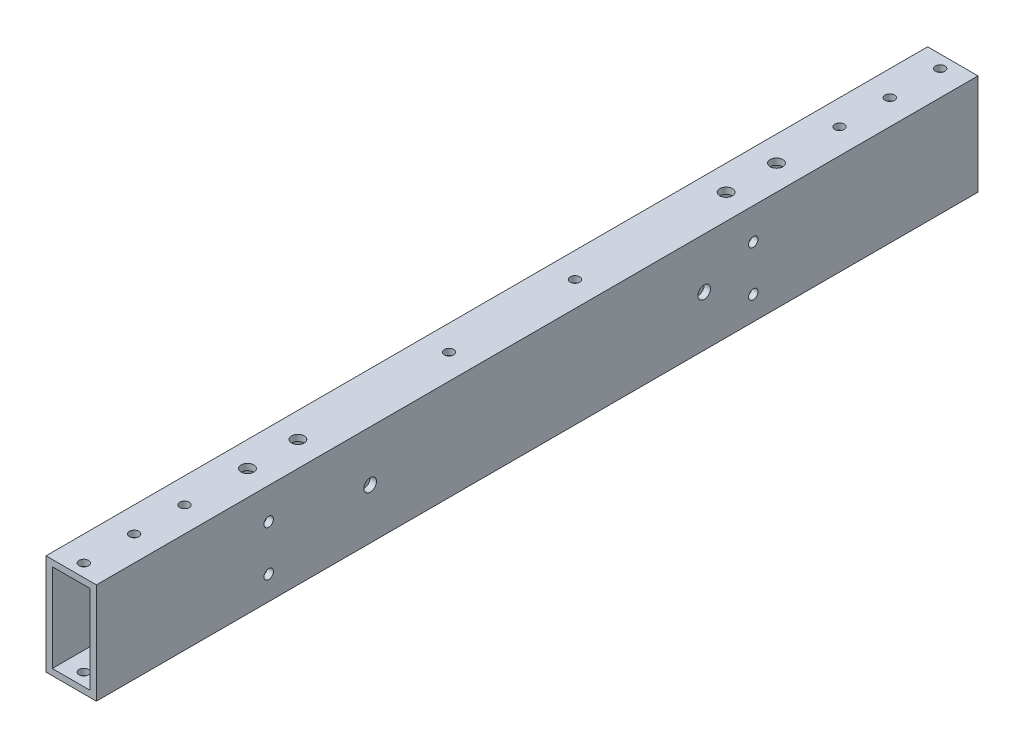
SolidWorks part; units mm, degrees
material "6063-T1"
ref_plane "Front Plane" through (0, 0, 0) normal (0, 0, 1) x (1, 0, 0)
ref_plane "Top Plane" through (0, 0, 0) normal (0, 1, 0) x (1, 0, 0)
ref_plane "Right Plane" through (0, 0, 0) normal (1, 0, 0) x (0, 0, -1)
sketch "Sketch1" plane through (0, 0, 0) normal (0, 0, 1) x (1, 0, 0)
  line L1 (-12.7, 25.4) -> (12.7, 25.4)
  line L2 (-12.7, 25.4) -> (-12.7, -25.4)
  line L3 (-12.7, -25.4) -> (12.7, -25.4)
  line L4 (12.7, 25.4) -> (12.7, -25.4)
  line L5 (-12.7, 25.4) -> (12.7, -25.4) construction
  line L6 (-12.7, -25.4) -> (12.7, 25.4) construction
  point P0 (0, 0)
  dimension "D1" = 25.4
  dimension "D2" = 50.8
extrude "Boss-Extrude1" add sketch "Sketch1" along normal blind 444.5
shell "Shell1" thickness 3.175 removed face at (0, 0, 0) removed face at (0, 0, 444.5)
sketch "Sketch2" plane through (0, 25.4, 0) normal (0, 1, 0) x (1, 0, 0)
  line L0 (12.7, 0) -> (-12.7, 0) construction
  line L1 (12.7, -222.25) -> (-14.2289, -222.25) construction
  line L2 (12.7, -444.5) -> (12.7, 0) construction
  circle A0 centre (0, -6.35) radius 2.3812
  circle A3 centre (0, -31.75) radius 2.3812
  circle A4 centre (0, -57.15) radius 2.3812
  circle A5 centre (0, -387.35) radius 2.3812
  circle A6 centre (0, -412.75) radius 2.3812
  circle A7 centre (0, -438.15) radius 2.3813
  dimension "D1" = 4.7625
  dimension "D2" = 6.35
  dimension "D3" = 3
extrude "Cut-Extrude1" cut sketch "Sketch2" against normal through all
sketch "Sketch3" plane through (-12.7, 0, 0) normal (-1, 0, 0) x (0, 0, 1)
  line L0 (222.25, 25.4) -> (222.25, -25.4) construction
  line L1 (444.5, 25.4) -> (0, 25.4) construction
  line L2 (444.5, -25.4) -> (0, -25.4) construction
  line L3 (0, 25.4) -> (0, -25.4) construction
  circle A0 centre (138.049, 0) radius 3.175
  circle A1 centre (306.451, 0) radius 3.175
  dimension "D1" = 6.35
  dimension "D2" = 138.049
  dimension "D3" = 25.4
extrude "Cut-Extrude2" cut sketch "Sketch3" against normal through all
sketch "Sketch4" plane through (0, 25.4, 0) normal (0, 1, 0) x (1, 0, 0)
  line L0 (12.7, -222.25) -> (-12.7, -222.25) construction
  line L1 (12.7, -444.5) -> (12.7, 0) construction
  line L2 (-12.7, -444.5) -> (-12.7, 0) construction
  line L3 (12.7, 0) -> (-12.7, 0) construction
  circle A0 centre (0, -190.5) radius 2.3812
  circle A1 centre (0, -254) radius 2.3813
  dimension "D1" = 4.7625
  dimension "D2" = 190.5
  dimension "D3" = 12.7
extrude "Cut-Extrude3" cut sketch "Sketch4" against normal through all
sketch "Sketch5" plane through (-12.7, 0, 0) normal (-1, 0, 0) x (0, 0, 1)
  line L1 (444.5, 25.4) -> (0, 25.4) construction
  line L2 (444.5, 25.4) -> (444.5, -25.4) construction
  line L3 (0, -25.4) -> (0, 25.4) construction
  circle A0 centre (357.632, 9.525) radius 2.3813
  circle A1 centre (357.632, -13.335) radius 2.3813
  circle A2 centre (113.284, 9.525) radius 2.3813
  circle A3 centre (113.284, -13.335) radius 2.3813
  dimension "D3" = 4.7625
  dimension "D4" = 4.7625
  dimension "D9" = 4.7625
  dimension "D10" = 4.7625
  dimension "D1" = 86.868
  dimension "D2" = 86.868
  dimension "D5" = 15.875
  dimension "D6" = 22.86
  dimension "D7" = 113.284
  dimension "D8" = 113.284
  dimension "D11" = 22.86
extrude "Cut-Extrude4" cut sketch "Sketch5" against normal through all
sketch "Sketch6" plane through (0, 25.4, 0) normal (0, 1, 0) x (1, 0, 0)
  line L0 (0, -444.5) -> (0, -342.9) construction
  line L1 (12.7, -444.5) -> (-12.7, -444.5) construction
  line L2 (0, -355.6) -> (0, -330.2) construction
  circle A0 centre (0, -330.2) radius 3.175
  circle A1 centre (0, -355.6) radius 3.175
  point P8 (0, -342.9)
  dimension "D3" = 6.35
  dimension "D4" = 6.35
  dimension "D1" = 101.6
  dimension "D2" = 12.7
extrude "Cut-Extrude5" cut sketch "Sketch6" against normal up to surface (3.175 mm away) up to face at (0, 22.225, 188.1188)
sketch "Sketch7" plane through (0, 25.4, 0) normal (0, 1, 0) x (1, 0, 0)
  line L0 (0, 0) -> (0, -101.6) construction
  line L1 (0, -114.3) -> (0, -88.9) construction
  circle A0 centre (0, -88.9) radius 3.175
  circle A1 centre (0, -114.3) radius 3.175
  point P6 (0, -101.6)
  dimension "D3" = 6.35
  dimension "D4" = 6.35
  dimension "D1" = 101.6
  dimension "D2" = 12.7
extrude "Cut-Extrude6" cut sketch "Sketch7" against normal up to surface (47.625 mm away) up to face at (0, -22.225, 192.8812)
